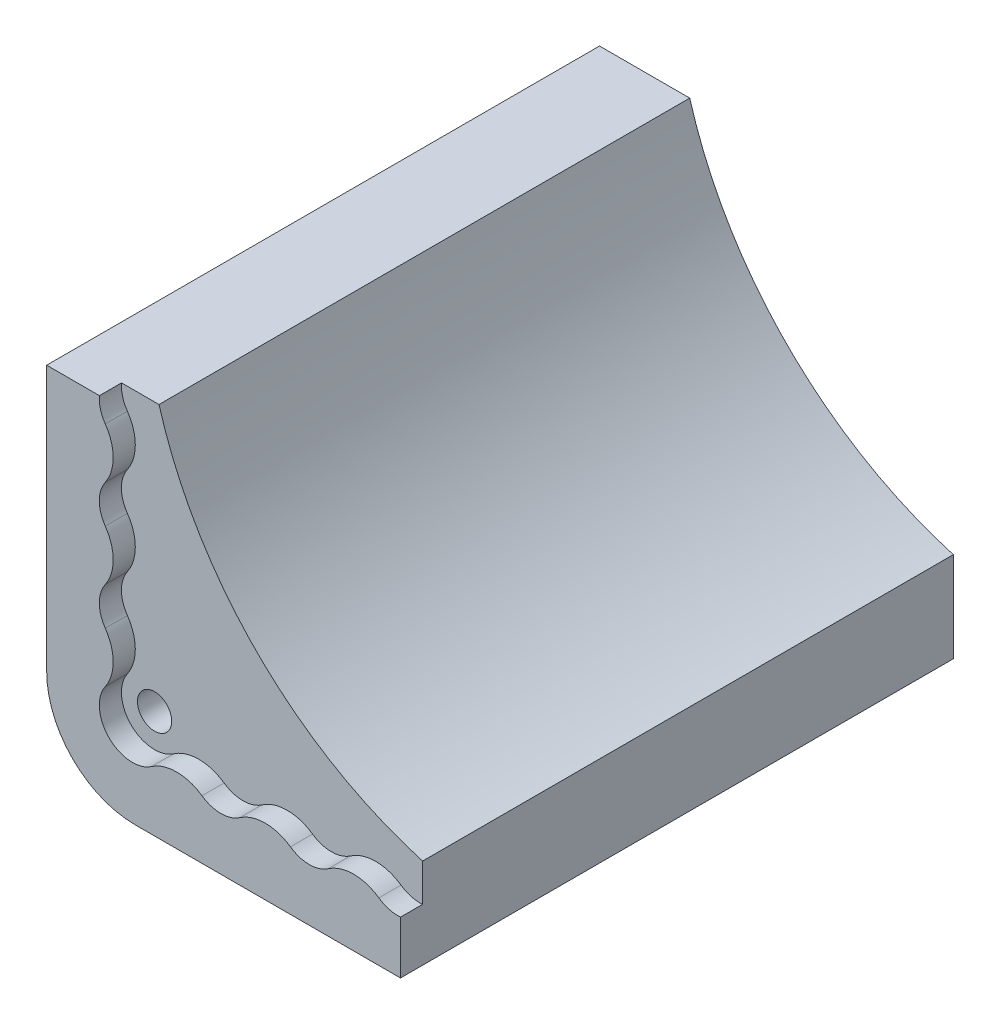
SolidWorks part; units mm, degrees
material "POM Acetal Copolymer"
ref_plane "Front Plane" through (0, 0, 0) normal (0, 0, 1) x (1, 0, 0)
ref_plane "Top Plane" through (0, 0, 0) normal (0, 1, 0) x (1, 0, 0)
ref_plane "Right Plane" through (0, 0, 0) normal (1, 0, 0) x (0, 0, -1)
sketch "Sketch1" plane through (0, 0, 0) normal (0, 0, 1) x (1, 0, 0)
  line L0 (0, 0) -> (50.8, 0)
  line L1 (50.8, 0) -> (50.8, 25.4)
  line L2 (50.8, 25.4) -> (25.4, 25.4)
  line L3 (25.4, 25.4) -> (25.4, 50.8)
  line L4 (25.4, 50.8) -> (0, 50.8)
  line L5 (0, 50.8) -> (0, 0)
  dimension "D1" = 25.4
  dimension "D2" = 25.4
extrude "Boss-Extrude1" add sketch "Sketch1" along normal blind 79.375
hole_wizard "#10 (0.1935) Diameter Hole1" positions "3DSketch1" profile "Sketch3" hole size "#10" standard "ANSI Inch" end condition up to next
sketch3d "3DSketch1"
  line L2 (0, 12.319, 79.375) -> (12.319, 12.319, 79.375) construction
  line L3 (0, 50.8, 79.375) -> (0, 0, 79.375) construction
  line L4 (12.319, 12.319, 79.375) -> (12.319, 0, 79.375) construction
  line L5 (0, 0, 79.375) -> (50.8, 0, 79.375) construction
  point P0 (12.319, 12.319, 79.375)
  dimension "D1" = 12.319
sketch "Sketch3" plane through (12.319, 12.319, 79.375) normal (1, 0, 0) x (0, -1, 0)
  line L0 (0, 0) -> (0, 79.375)
  line L1 (0, 79.375) -> (2.4574, 79.375)
  line L2 (2.4574, 79.375) -> (2.4574, 0)
  line L5 (2.4574, 0) -> (0, 0)
  line L11 (0, -6.35) -> (0, 107.95) construction
  dimension "Thru Hole Dia." = 4.9149
  dimension "Thru Hole Depth" = 79.375
sketch "Sketch4" plane through (0, 0, 79.375) normal (0, 0, 1) x (1, 0, 0)
  line L2 (0, 0) -> (50.8, 0) construction
  line L3 (0, 50.8) -> (0, 0) construction
  line L4 (7.5718, 50.8) -> (0, 50.8)
  line L5 (0, 50.8) -> (0, 12.7)
  line L6 (25.4, 50.8) -> (0, 50.8) construction
  line L9 (50.8, 0) -> (50.8, 25.4) construction
  line L10 (50.8, 0) -> (12.7, 0)
  line L11 (50.8, 7.5718) -> (50.8, 0)
  arc A13 (8.4106, 15.0404) -> (15.0404, 8.4106) centre (12.319, 12.319) ccw
  arc A14 (8.4106, 15.0404) -> (8.4106, 22.2976) centre (3.1995, 18.669) ccw
  arc A15 (8.4106, 27.7404) -> (8.4106, 22.2976) centre (12.319, 25.019) ccw
  arc A16 (8.4106, 27.7404) -> (8.4106, 34.9976) centre (3.1995, 31.369) ccw
  arc A18 (8.4106, 40.4404) -> (8.4106, 34.9976) centre (12.319, 37.719) ccw
  arc A19 (8.4106, 40.4404) -> (8.4106, 47.6976) centre (3.1995, 44.069) ccw
  arc A20 (7.5718, 50.8) -> (8.4106, 47.6976) centre (12.319, 50.419) ccw
  arc A22 (0, 12.7) -> (12.7, 0) centre (12.7, 12.7) ccw
  arc A23 (22.2976, 8.4106) -> (18.669, 9.5495) centre (18.669, 3.1995) ccw
  arc A24 (18.669, 9.5495) -> (15.0404, 8.4106) centre (18.669, 3.1995) ccw
  arc A25 (22.2976, 8.4106) -> (27.7404, 8.4106) centre (25.019, 12.319) ccw
  arc A26 (31.369, 9.5495) -> (27.7404, 8.4106) centre (31.369, 3.1995) ccw
  arc A27 (34.9976, 8.4106) -> (31.369, 9.5495) centre (31.369, 3.1995) ccw
  arc A28 (34.9976, 8.4106) -> (40.4404, 8.4106) centre (37.719, 12.319) ccw
  arc A29 (44.069, 9.5495) -> (40.4404, 8.4106) centre (44.069, 3.1995) ccw
  arc A30 (47.6976, 8.4106) -> (44.069, 9.5495) centre (44.069, 3.1995) ccw
  arc A31 (47.6976, 8.4106) -> (50.8, 7.5718) centre (50.419, 12.319) ccw
  circle M3 centre (12.319, 12.319) radius 2.4574
  line M4 (0, 50.8) -> (0, 0)
  line M5 (0, 0) -> (50.8, 0)
  line M6 (50.8, 0) -> (50.8, 25.4)
  line M7 (50.8, 25.4) -> (25.4, 25.4)
  line M8 (25.4, 25.4) -> (25.4, 50.8)
  line M9 (25.4, 50.8) -> (0, 50.8)
  dimension "D1" = 12.7
  dimension "D2" = 12.7
  dimension "D3" = 12.7
extrude "Cut-Extrude2" cut sketch "Sketch4" against normal through all contours A23 M4 M5 region at (2.8368, 2.8368, 79.375)
extrude "Cut-Extrude3" cut sketch "Sketch4<4>" against normal blind 3.175 contours L4 M9 M6 M7 M8 M3 region at (25.0828, 25.0828, 79.375)
sketch "Sketch4<4>" plane through (0, 0, 79.375) normal (0, 0, 1) x (1, 0, 0) same geometry as "Sketch4"
sketch "Sketch7" plane through (0, 0, 76.2) normal (0, 0, 1) x (1, 0, 0)
  line L0 (0, 50.8) -> (0, 12.7)
  line L1 (50.8, 0) -> (12.7, 0)
  line L2 (50.8, 12.954) -> (50.8, 0)
  line L3 (0, 50.8) -> (12.954, 50.8)
  line L4 (12.954, 50.8) -> (25.4, 50.8)
  line L5 (25.4, 50.8) -> (25.4, 28.7091)
  line L6 (28.7091, 25.4) -> (50.8, 25.4)
  line L7 (50.8, 25.4) -> (50.8, 12.954)
  line L9 (25.4, 50.8) -> (7.5718, 50.8) construction
  line L13 (50.8, 25.4) -> (25.4, 25.4) construction
  line L14 (25.4, 25.4) -> (25.4, 50.8) construction
  line L15 (0, 50.8) -> (0, 12.7) construction
  line L16 (12.7, 0) -> (50.8, 0) construction
  line L17 (50.8, 0) -> (50.8, 7.5718) construction
  line L18 (25.4, 28.7091) -> (25.4, 25.4)
  line L19 (25.4, 25.4) -> (28.7091, 25.4)
  arc A0 (12.954, 50.8) -> (50.8, 12.954) centre (66.3083, 66.3083) ccw
  arc A1 (0, 12.7) -> (12.7, 0) centre (12.7, 12.7) ccw
  arc A4 (0, 12.7) -> (12.7, 0) centre (12.7, 12.7) ccw construction
  point P8 (12.7, 12.7)
  line M9 (25.4, 50.8) -> (7.5718, 50.8)
  line M21 (50.8, 7.5718) -> (50.8, 25.4)
  line M22 (50.8, 25.4) -> (25.4, 25.4)
  line M23 (25.4, 25.4) -> (25.4, 50.8)
  dimension "D1" = 55.5625
  dimension "D2" = 12.954
  dimension "D3" = 12.954
extrude "Cut-Extrude5" cut sketch "Sketch7" against normal through all contours A0 M9 M23 | A0 M22 M21 region at (20.8556, 42.8288, 76.2) region at (42.8288, 20.8556, 76.2)
sketch "Sketch8" plane through (0, 0, 76.2) normal (0, 0, 1) x (1, 0, 0)
  arc A0 (25.4, 28.7091) -> (28.7091, 25.4) centre (66.3083, 66.3083) ccw
  arc A1 (12.954, 50.8) -> (25.4, 28.7091) centre (66.3083, 66.3083) ccw construction
extrude "Extrude-Thin1" add sketch "Sketch8" against normal up to surface (76.2 mm away) thin up to face at (14.7764, 12.319, 0) thin type one direction wall 2.54
